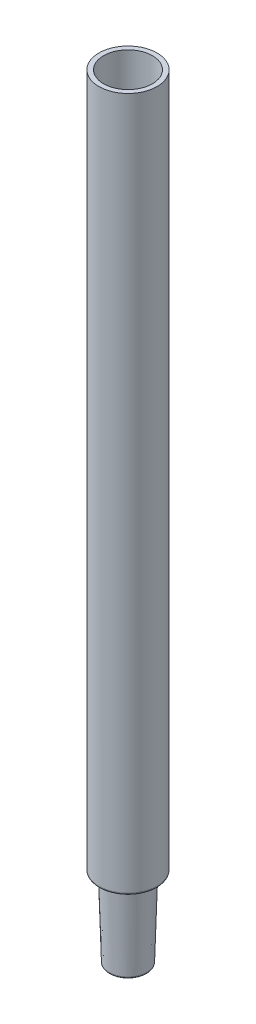
SolidWorks part; units mm, degrees
ref_plane "Ebene vorne" through (0, 0, 0) normal (0, 0, 1) x (1, 0, 0)
ref_plane "Ebene oben" through (0, 0, 0) normal (0, 1, 0) x (1, 0, 0)
ref_plane "Ebene rechts" through (0, 0, 0) normal (1, 0, 0) x (0, 0, -1)
sketch "Skizze1" plane through (0, 0, 0) normal (0, 0, 1) x (1, 0, 0)
  line L1 (-2.6, 82.5) -> (-3.1, 82.5)
  line L2 (-3.1, 82.5) -> (-3.1, 8.5)
  line L4 (0, 0) -> (0, -28.3945) construction
  line L14 (-2.6, 9) -> (-2.6, 82.5)
  line L15 (-2.6, 9) -> (-1.7647, 9)
  line L17 (-1.7647, 9) -> (-1.5, 0)
  line L18 (-1.5, 0) -> (-2, 0)
  line L19 (-2, 0) -> (-2.25, 8.5)
  line L21 (-2.25, 8.5) -> (-3.1, 8.5)
  point P6 (-2, 0)
  point P10 (0, 0)
  point P12 (-2.25, 7.9214)
  point P13 (-3.1, 7.949)
  point P14 (0, 0)
  point P15 (-1.7397, 8.903)
  dimension "D1" = 0.5
  dimension "D2" = 2.25
  dimension "D3" = 3.1
  dimension "D4" = 0.5
  dimension "D5" = 2
  dimension "D6" = 0.5
  dimension "D7" = 8.5
  dimension "D8" = 74
revolve "Rotation1" add sketch "Skizze1" angle 360 about L4
sketch "Skizze2" plane through (0, 82.5, 0) normal (0, 1, 0) x (1, 0, 0)
  circle A0 centre (0, 0) radius 3.1 construction
  circle A1 centre (0, 0) radius 2.6 construction
  circle A2 centre (0, 0) radius 2.6
  ellipse E0 centre (0, 0) end of major axis (10, 0) minor radius 3.1
  dimension "D1" = 20
extrude "Aufsatz-Linear austragen1" [suppressed] add sketch "Skizze2" against normal blind 1
fillet "Verrundung1" radius 0.2 4 edges at (-1.5, 0, 0) (-2, 0, 0) (-2.25, 8.5, 0) (-3.1, 8.5, 0)
